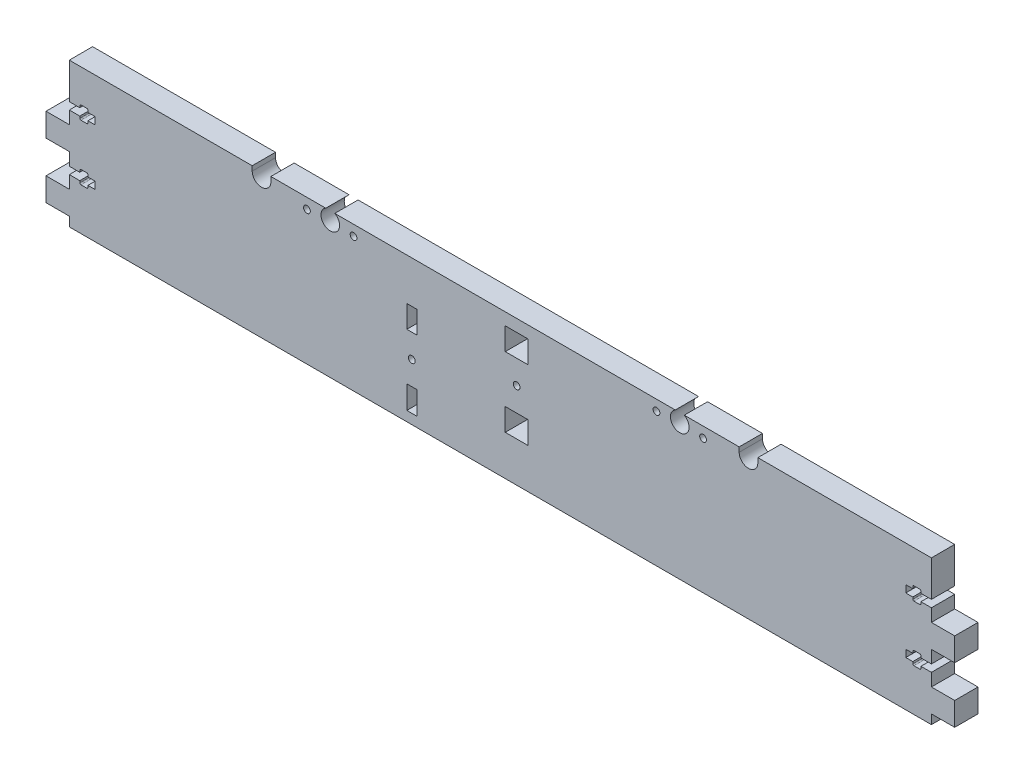
SolidWorks part; units mm, degrees
ref_plane "Front Plane" through (0, 0, 0) normal (0, 0, 1) x (1, 0, 0)
ref_plane "Top Plane" through (0, 0, 0) normal (0, 1, 0) x (1, 0, 0)
ref_plane "Right Plane" through (0, 0, 0) normal (1, 0, 0) x (0, 0, -1)
sketch "Sketch1" plane through (0, 0, 0) normal (0, 0, 1) x (1, 0, 0)
  line L0 (0, 0) -> (-185, 0)
  line L1 (-185, 0) -> (-185, -62) construction
  line L2 (0, -62) -> (-185, -62)
  line L3 (-185, -62) -> (-185, -58)
  line L4 (-185, -58) -> (-195, -58)
  line L5 (-195, -58) -> (-195, -48)
  line L6 (-195, -48) -> (-185, -48)
  line L7 (-185, -48) -> (-185, -34)
  line L8 (-185, -34) -> (-195, -34)
  line L9 (-195, -34) -> (-195, -24)
  line L10 (-195, -24) -> (-185, -24)
  line L11 (0, -62) -> (0, 0)
  line L12 (-185, -24) -> (-185, 0)
  line L13 (-195, -58) -> (-195, -24) construction
  line L14 (-195, -29) -> (-185, -29) construction
  line L15 (-195, -53) -> (-185, -53) construction
  dimension "D1" = 185
  dimension "D2" = 10
  dimension "D3" = 10
  dimension "D4" = 10
  dimension "D5" = 24
  dimension "D6" = 29
  dimension "D7" = 62
extrude "MainBody" add sketch "Sketch1" along normal blind 10
sketch "Sketch3" plane through (0, 0, 10) normal (0, 0, 1) x (1, 0, 0)
  line L0 (-185, -17) -> (-174, -17) construction
  line L1 (-185, 0) -> (-185, -24) construction
  line L2 (-185, -18.55) -> (-180.5, -18.55)
  line L3 (-180.5, -18.55) -> (-180.5, -19.35)
  line L4 (-180, -19.85) -> (-177.5, -19.85)
  line L5 (-177, -19.35) -> (-177, -18.55)
  line L6 (-177, -18.55) -> (-174, -18.55)
  line L7 (-174, -18.55) -> (-174, -15.45)
  line L8 (-180.5, -18.55) -> (-177, -18.55) construction
  line L9 (-195, -24) -> (-195, -34) construction
  line L10 (-180.5, -15.45) -> (-177, -15.45) construction
  line L11 (-177, -15.45) -> (-174, -15.45)
  line L12 (-177, -14.65) -> (-177, -15.45)
  line L13 (-180, -14.15) -> (-177.5, -14.15)
  line L14 (-180.5, -15.45) -> (-180.5, -14.65)
  line L15 (-185, -15.45) -> (-180.5, -15.45)
  line L16 (-185, -18.55) -> (-185, -15.45)
  line L17 (-185, -24) -> (-185, -34) construction
  line L19 (-195, -24) -> (-195, -34) construction
  line L20 (-195, -29) -> (-185, -29) construction
  line L21 (-180.5, -42.55) -> (-177, -42.55) construction
  line L22 (-180.5, -39.45) -> (-177, -39.45) construction
  line L23 (-185, -41) -> (-174, -41) construction
  line L24 (-185, -39.45) -> (-185, -42.55)
  line L25 (-185, -42.55) -> (-180.5, -42.55)
  line L26 (-180.5, -42.55) -> (-180.5, -43.35)
  line L27 (-180, -43.85) -> (-177.5, -43.85)
  line L28 (-177, -43.35) -> (-177, -42.55)
  line L29 (-177, -42.55) -> (-174, -42.55)
  line L30 (-174, -39.45) -> (-174, -42.55)
  line L31 (-177, -39.45) -> (-174, -39.45)
  line L32 (-177, -38.65) -> (-177, -39.45)
  line L33 (-180, -38.15) -> (-177.5, -38.15)
  line L34 (-180.5, -39.45) -> (-180.5, -38.65)
  line L35 (-185, -39.45) -> (-180.5, -39.45)
  line L36 (-180.5, -15.45) -> (-177, -15.45) construction
  arc A0 (-177.5, -19.85) -> (-177, -19.35) centre (-177.5, -19.35) ccw
  arc A1 (-180.5, -19.35) -> (-180, -19.85) centre (-180, -19.35) ccw
  arc A2 (-180.5, -14.65) -> (-180, -14.15) centre (-180, -14.65) cw
  arc A3 (-177.5, -14.15) -> (-177, -14.65) centre (-177.5, -14.65) cw
  arc A4 (-177.5, -43.85) -> (-177, -43.35) centre (-177.5, -43.35) ccw
  arc A5 (-180.5, -43.35) -> (-180, -43.85) centre (-180, -43.35) ccw
  arc A6 (-180.5, -38.65) -> (-180, -38.15) centre (-180, -38.65) cw
  arc A7 (-177.5, -38.15) -> (-177, -38.65) centre (-177.5, -38.65) cw
  point P6 (-195, -29)
  point P15 (-177, -19.85)
  point P18 (-180.5, -19.85)
  point P29 (-180.5, -14.15)
  point P30 (-177, -14.15)
  point P62 (-177, -43.85)
  point P63 (-180.5, -43.85)
  point P64 (-180.5, -38.15)
  point P65 (-177, -38.15)
  dimension "D2" = 8
  dimension "D7" = 0.5
  dimension "D1" = 11
  dimension "D3" = 1.55
  dimension "D4" = 2.85
  dimension "D5" = 12
  dimension "D6" = 3.5
extrude "ScrewCutouts" cut sketch "Sketch3" against normal through all
mirror "Mirror1" about plane through (0, 0, 0) normal (1, 0, 0) of "ScrewCutouts", "MainBody"
sketch "Sketch2" plane through (0, 0, 10) normal (0, 0, 1) x (1, 0, 0)
  line L0 (0, 0) -> (0, -62) construction
  line L1 (-185, -62) -> (185, -62) construction
  line L2 (2, 0) -> (2, -62) construction
  line L3 (185, 0) -> (-185, 0) construction
  line L4 (-63, -4.5) -> (-83, -4.5) construction
  line L5 (-73, -7.5) -> (-73, 0.5) construction
  line L6 (77, -7.5) -> (77, 0.5) construction
  line L7 (67, -4.5) -> (87, -4.5) construction
  circle A0 centre (-73, -3.5) radius 4
  circle A1 centre (-83, -4.5) radius 1.45
  circle A2 centre (-63, -4.5) radius 1.45
  circle A3 centre (67, -4.5) radius 1.45
  circle A4 centre (87, -4.5) radius 1.45
  circle A5 centre (77, -3.5) radius 4
  dimension "D1" = 2.9
  dimension "D2" = 8
  dimension "D4" = 3.5
  dimension "D5" = 75
  dimension "D6" = 2
  dimension "D3" = 10
  dimension "D7" = 1
extrude "RodCutouts" cut sketch "Sketch2" against normal through all
sketch "Sketch4" plane through (0, 0, 10) normal (0, 0, 1) x (1, 0, 0)
  line L0 (77, -3.5) -> (-73, -3.5) construction
  line L1 (2, -3.5) -> (2, -62) construction
  line L2 (-185, -62) -> (185, -62) construction
  line L3 (7, -44.8) -> (7, -5.2) construction
  line L4 (75.0635, 0) -> (-71.0635, 0) construction
  line L5 (7, -10) -> (7, -40) construction
  line L6 (2.1, -5.2) -> (11.9, -5.2)
  line L7 (2.1, -5.2) -> (2.1, -14.8)
  line L8 (2.1, -14.8) -> (11.9, -14.8)
  line L9 (11.9, -5.2) -> (11.9, -14.8)
  line L10 (2.1, -5.2) -> (11.9, -14.8) construction
  line L11 (2.1, -14.8) -> (11.9, -5.2) construction
  line L12 (2.1, -35.2) -> (11.9, -35.2)
  line L13 (2.1, -35.2) -> (2.1, -44.8)
  line L14 (2.1, -44.8) -> (11.9, -44.8)
  line L15 (11.9, -35.2) -> (11.9, -44.8)
  line L16 (2.1, -35.2) -> (11.9, -44.8) construction
  line L17 (2.1, -44.8) -> (11.9, -35.2) construction
  circle A0 centre (7, -25) radius 1.45
  point P12 (7, -10)
  point P17 (7, -40)
  dimension "D8" = 2.9
  dimension "D1" = 9.8
  dimension "D2" = 9.6
  dimension "D3" = 9.8
  dimension "D4" = 9.6
  dimension "D5" = 30
  dimension "D6" = 10
  dimension "D7" = 5
extrude "Cut-Extrude3" cut sketch "Sketch4" against normal through all
sketch "Sketch5" plane through (0, 0, 10) normal (0, 0, 1) x (1, 0, 0)
  line L0 (-38, 0) -> (-38, -62) construction
  line L1 (-74.9365, 0) -> (-185, 0) construction
  line L2 (-185, -62) -> (185, -62) construction
  line L3 (-40.15, -27.625) -> (-40.15, -47.875) construction
  line L4 (-40.15, -18.025) -> (-35.85, -18.025)
  line L5 (-40.15, -18.025) -> (-40.15, -27.625)
  line L6 (-40.15, -27.625) -> (-35.85, -27.625)
  line L7 (-35.85, -18.025) -> (-35.85, -27.625)
  line L8 (-40.15, -18.025) -> (-35.85, -27.625) construction
  line L9 (-40.15, -27.625) -> (-35.85, -18.025) construction
  line L10 (-40.15, -47.875) -> (-35.85, -47.875)
  line L11 (-40.15, -47.875) -> (-40.15, -57.775)
  line L12 (-40.15, -57.775) -> (-35.85, -57.775)
  line L13 (-35.85, -47.875) -> (-35.85, -57.775)
  line L14 (-40.15, -47.875) -> (-35.85, -57.775) construction
  line L15 (-40.15, -57.775) -> (-35.85, -47.875) construction
  line L16 (-35.85, -47.875) -> (-35.85, -27.625) construction
  line L17 (-40.15, -37.75) -> (-35.85, -37.75) construction
  line L18 (-73, -3.5) -> (77, -3.5) construction
  line L19 (2, -3.5) -> (2, -62) construction
  line L20 (2, -32.75) -> (-195, -32.75) construction
  line L21 (-195, -24) -> (-195, -34) construction
  line L22 (-31.65, 8.9944) -> (-31.65, 5) construction
  line L23 (75.0635, 0) -> (-71.0635, 0) construction
  line L24 (-28.45, 8.9944) -> (-28.45, 5)
  line L25 (-34.85, 8.9944) -> (-34.85, 5)
  circle A0 centre (-38, -37.75) radius 1.45
  arc A1 (-28.45, 8.9944) -> (-34.85, 8.9944) centre (-31.65, 8.9944) ccw
  arc A2 (-34.85, 5) -> (-28.45, 5) centre (-31.65, 5) ccw
  point P6 (-38, -22.825)
  point P11 (-38, -52.825)
  point P34 (-31.65, 6.9972)
  dimension "D4" = 9.6
  dimension "D5" = 30
  dimension "D6" = 2.9
  dimension "D9" = 3.2
  dimension "D1" = 4.3
  dimension "D2" = 0
  dimension "D3" = 9.9
  dimension "D7" = 40
  dimension "D8" = 5
  dimension "D10" = 5
  dimension "D11" = 1
extrude "EndstopHolder" cut sketch "Sketch5" against normal through all
sketch "Sketch6" plane through (0, 0, 10) normal (0, 0, 1) x (1, 0, 0)
  line L0 (-40.15, -47.875) -> (-40.15, -27.625) construction
  line L1 (-42.35, -47.875) -> (-27.85, -47.875) construction
  line L3 (-27.85, -53.875) -> (-27.85, -41.875) construction
  line L4 (-29.85, -53.875) -> (-29.85, -41.875)
  line L5 (-25.85, -53.875) -> (-25.85, -41.875)
  line L6 (-35.85, -47.875) -> (-40.15, -47.875) construction
  line L7 (-35.85, -57.775) -> (-35.85, -47.875) construction
  arc A0 (-29.85, -53.875) -> (-25.85, -53.875) centre (-27.85, -53.875) ccw
  arc A1 (-25.85, -41.875) -> (-29.85, -41.875) centre (-27.85, -41.875) ccw
  point P10 (-27.85, -47.875)
  dimension "D1" = 2
  dimension "D2" = 12
  dimension "D3" = 8
  dimension "D4" = 0
extrude "EndstopWires" [suppressed] cut sketch "Sketch6" against normal through all
sketch "Sketch7" plane through (0, 0, 10) normal (0, 0, 1) x (1, 0, 0)
  line L0 (-73, -3.5) -> (77, -3.5) construction
  line L1 (2, -3.5) -> (2, -62) construction
  line L3 (-102.5, 0) -> (-102.5, -2) construction
  line L4 (-74.9365, 0) -> (-185, 0) construction
  line L5 (-98.5, 0) -> (-98.5, -2)
  line L6 (-106.5, 0) -> (-106.5, -2)
  line L7 (106.5, 0) -> (106.5, -2) construction
  line L8 (102.5, 0) -> (102.5, -2)
  line L9 (110.5, 0) -> (110.5, -2)
  line L10 (-185, -62) -> (185, -62) construction
  arc A0 (-98.5, 0) -> (-106.5, 0) centre (-102.5, 0) ccw
  arc A1 (-106.5, -2) -> (-98.5, -2) centre (-102.5, -2) ccw
  arc A2 (102.5, 0) -> (110.5, 0) centre (106.5, 0) cw
  arc A3 (110.5, -2) -> (102.5, -2) centre (106.5, -2) cw
  point P12 (-102.5, -1)
  point P19 (106.5, -1)
  dimension "D3" = 4
  dimension "D1" = 2
  dimension "D2" = 104.5
extrude "Cut-Extrude4" cut sketch "Sketch7" against normal through all
equation "\"Y-ROD-SPACING\"=75"
equation "\"D5@Sketch2\"=\"Y-ROD-SPACING\""
equation "\"Y-BED-OFFSET\"=2"
equation "\"D6@Sketch2\"=\"Y-BED-OFFSET\""
equation "\"T-SLOT-NUT-FILLET-RADIUS\"=0.5"
equation "\"D7@Sketch3\"=\"T-SLOT-NUT-FILLET-RADIUS\""
equation "\"T-SLOT-SCREW-SHAFT-RADIUS\"=1.55"
equation "\"D3@Sketch3\"=\"T-SLOT-SCREW-SHAFT-RADIUS\""
equation "\"T-SLOT-SCREW-SHAFT-CUTOUT-LENGTH\"=11.0"
equation "\"D1@Sketch3\"=\"T-SLOT-SCREW-SHAFT-CUTOUT-LENGTH\""
equation "\"T-SLOT-NUT-DEPTH\"=3.5"
equation "\"D6@Sketch3\"=\"T-SLOT-NUT-DEPTH\""
equation "\"T-SLOT-NUT-WIDTH\"=2.85"
equation "\"D4@Sketch3\"=\"T-SLOT-NUT-WIDTH\""
equation "\"T-SLOT-NUT-END-DISTANCE\"=8"
equation "\"D2@Sketch3\"=\"T-SLOT-NUT-END-DISTANCE\""
equation "\"ACRYLIC-TAB-CUTOUT-SIZE\"=\"ACRYLIC-THICKNESS\"+\"ACRYLIC-TAB-TOLERANCE\"*2"
equation "\"D1@Sketch4\"=\"ACRYLIC-THICKNESS\"-\"KERF\"*2"
equation "\"D2@Sketch4\"=\"ACRYLIC-TAB-WIDTH\"-\"KERF\"*4"
equation "\"D3@Sketch4\"=\"ACRYLIC-THICKNESS\"-\"KERF\"*2"
equation "\"D4@Sketch4\"=\"ACRYLIC-TAB-WIDTH\"-\"KERF\"*4"
equation "\"ACRYLIC-M3-HOLE\"=2.9"
equation "\"D8@Sketch4\"=\"ACRYLIC-M3-HOLE\""
equation "\"Y-BED-ROD-INSET\"=3.5"
equation "\"D1@Sketch2\"=\"ACRYLIC-M3-HOLE\""
equation "\"D4@Sketch2\"=\"Y-BED-ROD-INSET\""
equation "\"SMOOTHROD-CAP-SCREW-DISTANCE\"=20"
equation "\"D3@Sketch2\"=\"SMOOTHROD-CAP-SCREW-DISTANCE\"/2"
equation "\"ACRYLIC-TAB-WIDTH\"=\"ACRYLIC-THICKNESS\""
equation "\"FRAME-WIDTH-INNER\"=370"
equation "\"D2@Sketch1\"=\"ACRYLIC-TAB-WIDTH\""
equation "\"D3@Sketch1\"=\"ACRYLIC-TAB-WIDTH\""
equation "\"D4@Sketch1\"=\"ACRYLIC-TAB-WIDTH\""
equation "\"D1@Sketch1\"=\"FRAME-WIDTH-INNER\"/2"
equation "\"X-ROD-SPACING\"=45"
equation "\"Z-ROD-SPACING\"=17.5"
equation "\"ACRYLIC-THICKNESS\"=10"
equation "\"ACRYLIC-THICKNESS2\"=4.5"
equation "\"NEMA17-HOLE-SPACING\"=31"
equation "\"NEMA17-CENTRAL-CUTOUT\"=22.5"
equation "\"Z-BRACKET-REACH\"=55"
equation "\"TOP-BRACKET-SPACING\"=40"
equation "\"SMOOTHROD-X-LENGTH\"=350"
equation "\"SMOOTHROD-Y-LENGTH\"=350"
equation "\"SMOOTHROD-Z-LENGTH\"=350"
equation "\"SMOOTHROD-TIGHTENING-HEADROOM\"=.25"
equation "\"LEADSCREW-Z-LENGTH\"=300"
equation "\"SCREW-LENGTH-FRAME\"=\"ACRYLIC-THICKNESS\" + 10"
equation "\"SCREW-HEAD-RADIUS\"=6"
equation "\"PRINTED-X-SMOOTHROD-DIAMETER\"=9.0"
equation "\"PRINTED-X-SMOOTHROD-CUTOUT\"=10"
equation "\"PRINTED-X-BASE-HEIGHT\"=10"
equation "\"PRINTED-LM8UU-CUTOUT-SIZE\"=15.5"
equation "\"PRINTED-LM8UU-CUTOUT-LENGTH\"=24.5"
equation "\"PRINTED-X-IDLER-HEIGHT\"=16"
equation "\"PSU-MOUNTING-WIDTH\"=95"
equation "\"PSU-MOUNTING-HEIGHT\"=177"
equation "\"D1@MainBody\"=\"ACRYLIC-THICKNESS\""
equation "\"D1@Sketch5\"=\"ACRYLIC-THICKNESS2\"-\"KERF\"*2"
equation "\"D3@Sketch5\"=\"ACRYLIC-TAB-CUTOUT-SIZE\""
equation "\"D4@Sketch5\"=\"ACRYLIC-TAB-WIDTH\"-\"KERF\"*4"
equation "\"D6@Sketch5\"=\"ACRYLIC-M3-HOLE\""
equation "\"Y-BED-SCREW-SPACING\"=209"
equation "\"Y-BED-SCREW-CUTOUT-SLOT-HEIGHT\"=2"
equation "\"Z-ROD-INSET\"=16"
equation "\"Y-BELT-TO-ROD-DISTANCE\"=20"
equation "\"SPOOL-HOLDER-ROD-SPACING\"=150"
equation "\"D1@Sketch7\"=\"Y-BED-SCREW-CUTOUT-SLOT-HEIGHT\""
equation "\"D2@Sketch7\"=\"Y-BED-SCREW-SPACING\"/2"
equation "\"ACRYLIC-TAB-TOLERANCE\"=-.05"
equation "\"SCREW-LENGTH-MOTOR\"=\"ACRYLIC-THICKNESS\" + 5"
equation "\"SCREW-LENGTH-EXTRUDER\"=28"
equation "\"ACRYLIC-X-CARRIAGE-WIDTH\"=55"
equation "\"ACRYLIC-X-CARRIAGE-HEIGHT\"=75"
equation "\"ACRYLIC-X-CARRIAGE-LM8UU-CUTOUT-WIDTH\"=24.25"
equation "\"ACRYLIC-X-CARRIAGE-SCREW-SPACING-X\"=15"
equation "\"ACRYLIC-X-CARRIAGE-SCREW-SPACING-Y\"=33"
equation "\"ACRYLIC-X-CARRIAGE-CENTER-TAB-SPACING\"=14"
equation "\"ACRYLIC-X-CARRIAGE-EXTRUDER-OFFSET\"=26"
equation "\"ACRYLIC-X-CARRIAGE-EXTRUDER-ANGLE\"=90"
equation "\"ACRYLIC-X-CARRIAGE-EXTRUDER-SHELF-DEPTH\"=\"ACRYLIC-X-CARRIAGE-EXTRUDER-OFFSET\" + 28"
equation "\"ACRYLIC-X-CARRIAGE-EXTRUDER-BRACE-SPACING\"=23"
equation "\"ACRYLIC-X-CARRIAGE-EXTRUDER-BRACE-TAB-OFFSET\"=20"
equation "\"ACRYLIC-X-CARRIAGE-EXTRUDER-BRACE-HEIGHT\"=35"
equation "\"ACRYLIC-X-CARRIAGE-EXTRUDER-BRACE-SCREW-SPACING\"=22"
equation "\"PRINTED-M3-HOLE\"=3.5"
equation "\"ACRYLIC-X-CARRIAGE-LM8UU-CUTOUT-HEIGHT\"=11.0"
equation "\"ACRYLIC-X-CARRIAGE-DUAL-WIDTH-MULTIPLIER\"=1.65"
equation "\"ACRYLIC-X-CARRIAGE-DUAL-HOTEND-SPACING\"=42"
equation "\"ACRYLIC-X-CARRIAGE-DUAL-WIDTH\"=75"
equation "\"ACRYLIC-X-CARRIAGE-DUAL-HOTEND-SEPARATION\"=36"
equation "\"ACRYLIC-X-CARRIAGE-DUAL-MOUNT-PLATE-DEPTH\"=75"
equation "\"ACRYLIC-X-CARRIAGE-DUAL-MOUNT-BRACE-WIDTH\"=33"
equation "\"ACRYLIC-X-CARRIAGE-DUAL-MOUNT-SCREW-WIDTH\"=40"
equation "\"BLOWER-FAN-WIDTH\"=15"
equation "\"KERF\"=0.1"
equation "\"PRINTED-M3-NUT-AF\"=6.25"
equation "\"ACRYLIC-X-CARRIAGE-DUAL-FAN-OFFSET\"=52"
equation "\"ACRYLIC-X-CARRIAGE-DUAL-FAN-HEIGHT\"=20"
